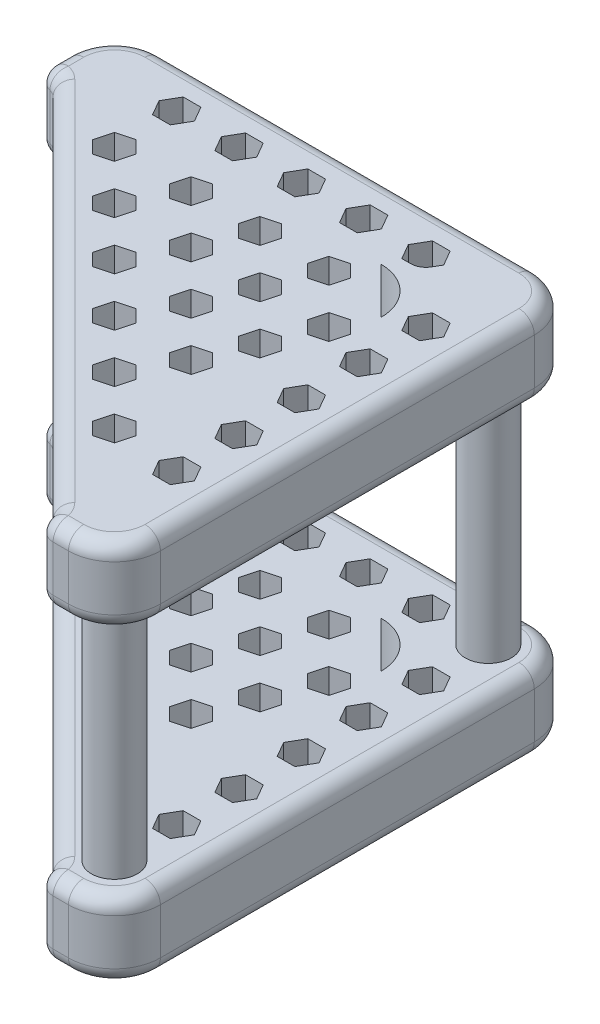
SolidWorks part; units mm, degrees
ref_plane "Front Plane" through (0, 0, 0) normal (0, 0, 1) x (1, 0, 0)
ref_plane "Top Plane" through (0, 0, 0) normal (0, 1, 0) x (1, 0, 0)
ref_plane "Right Plane" through (0, 0, 0) normal (1, 0, 0) x (0, 0, -1)
sketch "Sketch1" plane through (0, 0, 0) normal (0, 1, 0) x (1, 0, 0)
  line L0 (-9.7, 17.7) -> (14.7, 17.7)
  line L5 (17.7, -9.7) -> (17.7, 14.7)
  line L6 (-12.7, 14.7) -> (-12.7, 13.7)
  line L7 (13.7, -12.7) -> (14.7, -12.7)
  line L12 (-12.7, 14.7) -> (17.7, 14.7) construction
  line L13 (14.7, 17.7) -> (14.7, -12.7) construction
  line L14 (-4.4786, 14.7) -> (-5.056, 15.7)
  line L21 (-5.056, 15.7) -> (-6.2107, 15.7)
  line L22 (-6.2107, 15.7) -> (-6.788, 14.7)
  line L23 (-6.788, 14.7) -> (-6.2107, 13.7)
  line L24 (-6.2107, 13.7) -> (-5.056, 13.7)
  line L25 (-5.056, 13.7) -> (-4.4786, 14.7)
  line L26 (-0.412, 14.7) -> (-0.9893, 15.7)
  line L27 (-0.9893, 15.7) -> (-2.144, 15.7)
  line L28 (-2.144, 15.7) -> (-2.7214, 14.7)
  line L29 (-2.7214, 14.7) -> (-2.144, 13.7)
  line L30 (-2.144, 13.7) -> (-0.9893, 13.7)
  line L31 (-0.9893, 13.7) -> (-0.412, 14.7)
  line L32 (3.6547, 14.7) -> (3.0774, 15.7)
  line L33 (3.0774, 15.7) -> (1.9226, 15.7)
  line L34 (1.9226, 15.7) -> (1.3453, 14.7)
  line L35 (1.3453, 14.7) -> (1.9226, 13.7)
  line L36 (1.9226, 13.7) -> (3.0774, 13.7)
  line L37 (3.0774, 13.7) -> (3.6547, 14.7)
  line L38 (7.7214, 14.7) -> (7.144, 15.7)
  line L39 (7.144, 15.7) -> (5.9893, 15.7)
  line L40 (5.9893, 15.7) -> (5.412, 14.7)
  line L41 (5.412, 14.7) -> (5.9893, 13.7)
  line L42 (5.9893, 13.7) -> (7.144, 13.7)
  line L43 (7.144, 13.7) -> (7.7214, 14.7)
  line L44 (11.788, 14.7) -> (11.2107, 15.7)
  line L45 (11.2107, 15.7) -> (10.056, 15.7)
  line L46 (10.056, 15.7) -> (9.4786, 14.7)
  line L47 (9.4786, 14.7) -> (10.056, 13.7)
  line L48 (10.056, 13.7) -> (11.2107, 13.7)
  line L49 (11.2107, 13.7) -> (11.788, 14.7)
  line L56 (15.8547, 10.6333) -> (15.2774, 11.6333)
  line L57 (15.2774, 11.6333) -> (14.1226, 11.6333)
  line L58 (14.1226, 11.6333) -> (13.5453, 10.6333)
  line L59 (13.5453, 10.6333) -> (14.1226, 9.6333)
  line L60 (14.1226, 9.6333) -> (15.2774, 9.6333)
  line L61 (15.2774, 9.6333) -> (15.8547, 10.6333)
  line L62 (15.8547, 6.5667) -> (15.2774, 7.5667)
  line L63 (15.2774, 7.5667) -> (14.1226, 7.5667)
  line L64 (14.1226, 7.5667) -> (13.5453, 6.5667)
  line L65 (13.5453, 6.5667) -> (14.1226, 5.5667)
  line L66 (14.1226, 5.5667) -> (15.2774, 5.5667)
  line L67 (15.2774, 5.5667) -> (15.8547, 6.5667)
  line L68 (15.8547, 2.5) -> (15.2774, 3.5)
  line L69 (15.2774, 3.5) -> (14.1226, 3.5)
  line L70 (14.1226, 3.5) -> (13.5453, 2.5)
  line L71 (13.5453, 2.5) -> (14.1226, 1.5)
  line L72 (14.1226, 1.5) -> (15.2774, 1.5)
  line L73 (15.2774, 1.5) -> (15.8547, 2.5)
  line L74 (15.8547, -1.5667) -> (15.2774, -0.5667)
  line L75 (15.2774, -0.5667) -> (14.1226, -0.5667)
  line L76 (14.1226, -0.5667) -> (13.5453, -1.5667)
  line L77 (13.5453, -1.5667) -> (14.1226, -2.5667)
  line L78 (14.1226, -2.5667) -> (15.2774, -2.5667)
  line L79 (15.2774, -2.5667) -> (15.8547, -1.5667)
  line L80 (15.8547, -5.6333) -> (15.2774, -4.6333)
  line L81 (15.2774, -4.6333) -> (14.1226, -4.6333)
  line L82 (14.1226, -4.6333) -> (13.5453, -5.6333)
  line L83 (13.5453, -5.6333) -> (14.1226, -6.6333)
  line L84 (14.1226, -6.6333) -> (15.2774, -6.6333)
  line L85 (15.2774, -6.6333) -> (15.8547, -5.6333)
  line L92 (-11.4632, 12.4632) -> (12.4632, -11.4632)
  line L93 (9.7, 12.7) -> (12.7, 9.7)
  line L94 (-5.6333, 15.7) -> (-5.6333, 6.6333) construction
  line L95 (-5.6333, 6.6333) -> (15.8547, 10.6333) construction
  line L96 (-5.6333, 10.6333) -> (12.7, -7.7) construction
  line L97 (-1.6349, 6.6349) -> (-1.336, 7.7502)
  line L98 (-4.8168, 9.8168) -> (-4.518, 10.9322)
  line L99 (-4.518, 10.9322) -> (-5.3345, 11.7487)
  line L100 (-5.3345, 11.7487) -> (-6.4498, 11.4498)
  line L101 (-6.4498, 11.4498) -> (-6.7487, 10.3345)
  line L102 (-6.7487, 10.3345) -> (-5.9322, 9.518)
  line L103 (-5.9322, 9.518) -> (-4.8168, 9.8168)
  line L104 (-1.336, 7.7502) -> (-2.1525, 8.5667)
  line L105 (-2.1525, 8.5667) -> (-3.2678, 8.2678)
  line L106 (-3.2678, 8.2678) -> (-3.5667, 7.1525)
  line L107 (-3.5667, 7.1525) -> (-2.7502, 6.336)
  line L108 (-2.7502, 6.336) -> (-1.6349, 6.6349)
  line L109 (1.5471, 3.4529) -> (1.846, 4.5682)
  line L110 (1.846, 4.5682) -> (1.0295, 5.3847)
  line L111 (1.0295, 5.3847) -> (-0.0859, 5.0859)
  line L112 (-0.0859, 5.0859) -> (-0.3847, 3.9705)
  line L113 (-0.3847, 3.9705) -> (0.4318, 3.154)
  line L114 (0.4318, 3.154) -> (1.5471, 3.4529)
  line L115 (4.7291, 0.2709) -> (5.028, 1.3863)
  line L116 (5.028, 1.3863) -> (4.2115, 2.2027)
  line L117 (4.2115, 2.2027) -> (3.0961, 1.9039)
  line L118 (3.0961, 1.9039) -> (2.7973, 0.7885)
  line L119 (2.7973, 0.7885) -> (3.6137, -0.028)
  line L120 (3.6137, -0.028) -> (4.7291, 0.2709)
  line L121 (7.9111, -2.9111) -> (8.2099, -1.7957)
  line L122 (8.2099, -1.7957) -> (7.3934, -0.9792)
  line L123 (7.3934, -0.9792) -> (6.2781, -1.2781)
  line L124 (6.2781, -1.2781) -> (5.9792, -2.3934)
  line L125 (5.9792, -2.3934) -> (6.7957, -3.2099)
  line L126 (6.7957, -3.2099) -> (7.9111, -2.9111)
  line L127 (11.0931, -6.0931) -> (11.3919, -4.9777)
  line L128 (11.3919, -4.9777) -> (10.5754, -4.1612)
  line L129 (10.5754, -4.1612) -> (9.4601, -4.4601)
  line L130 (9.4601, -4.4601) -> (9.1612, -5.5754)
  line L131 (9.1612, -5.5754) -> (9.9777, -6.3919)
  line L132 (9.9777, -6.3919) -> (11.0931, -6.0931)
  line L133 (0.1832, 9.8168) -> (0.482, 10.9322)
  line L134 (0.482, 10.9322) -> (-0.3345, 11.7487)
  line L135 (-0.3345, 11.7487) -> (-1.4498, 11.4498)
  line L136 (-1.4498, 11.4498) -> (-1.7487, 10.3345)
  line L137 (-1.7487, 10.3345) -> (-0.9322, 9.518)
  line L138 (-0.9322, 9.518) -> (0.1832, 9.8168)
  line L139 (3.3651, 6.6349) -> (3.664, 7.7502)
  line L140 (3.664, 7.7502) -> (2.8475, 8.5667)
  line L141 (2.8475, 8.5667) -> (1.7322, 8.2678)
  line L142 (1.7322, 8.2678) -> (1.4333, 7.1525)
  line L143 (1.4333, 7.1525) -> (2.2498, 6.336)
  line L144 (2.2498, 6.336) -> (3.3651, 6.6349)
  line L145 (6.5471, 3.4529) -> (6.846, 4.5682)
  line L146 (6.846, 4.5682) -> (6.0295, 5.3847)
  line L147 (6.0295, 5.3847) -> (4.9141, 5.0859)
  line L148 (4.9141, 5.0859) -> (4.6153, 3.9705)
  line L149 (4.6153, 3.9705) -> (5.4318, 3.154)
  line L150 (5.4318, 3.154) -> (6.5471, 3.4529)
  line L151 (9.7291, 0.2709) -> (10.028, 1.3863)
  line L152 (10.028, 1.3863) -> (9.2115, 2.2027)
  line L153 (9.2115, 2.2027) -> (8.0961, 1.9039)
  line L154 (8.0961, 1.9039) -> (7.7973, 0.7885)
  line L155 (7.7973, 0.7885) -> (8.6137, -0.028)
  line L156 (8.6137, -0.028) -> (9.7291, 0.2709)
  line L157 (4.6832, 9.8168) -> (4.982, 10.9322)
  line L158 (4.982, 10.9322) -> (4.1655, 11.7487)
  line L159 (4.1655, 11.7487) -> (3.0502, 11.4498)
  line L160 (3.0502, 11.4498) -> (2.7513, 10.3345)
  line L161 (2.7513, 10.3345) -> (3.5678, 9.518)
  line L162 (3.5678, 9.518) -> (4.6832, 9.8168)
  line L163 (7.8651, 6.6349) -> (8.164, 7.7502)
  line L164 (8.164, 7.7502) -> (7.3475, 8.5667)
  line L165 (7.3475, 8.5667) -> (6.2322, 8.2678)
  line L166 (6.2322, 8.2678) -> (5.9333, 7.1525)
  line L167 (5.9333, 7.1525) -> (6.7498, 6.336)
  line L168 (6.7498, 6.336) -> (7.8651, 6.6349)
  line L169 (11.0471, 3.4529) -> (11.346, 4.5682)
  line L170 (11.346, 4.5682) -> (10.5295, 5.3847)
  line L171 (10.5295, 5.3847) -> (9.4141, 5.0859)
  line L172 (9.4141, 5.0859) -> (9.1153, 3.9705)
  line L173 (9.1153, 3.9705) -> (9.9318, 3.154)
  line L174 (9.9318, 3.154) -> (11.0471, 3.4529)
  line L175 (9.1832, 9.8168) -> (9.482, 10.9322)
  line L176 (9.482, 10.9322) -> (8.6655, 11.7487)
  line L177 (8.6655, 11.7487) -> (7.5502, 11.4498)
  line L178 (7.5502, 11.4498) -> (7.2513, 10.3345)
  line L179 (7.2513, 10.3345) -> (8.0678, 9.518)
  line L180 (8.0678, 9.518) -> (9.1832, 9.8168)
  line L181 (12.3651, 6.6349) -> (12.664, 7.7502)
  line L182 (12.664, 7.7502) -> (11.8475, 8.5667)
  line L183 (11.8475, 8.5667) -> (10.7322, 8.2678)
  line L184 (10.7322, 8.2678) -> (10.4333, 7.1525)
  line L185 (10.4333, 7.1525) -> (11.2498, 6.336)
  line L186 (11.2498, 6.336) -> (12.3651, 6.6349)
  arc A0 (9.7, 12.7) -> (12.7, 9.7) centre (9.7, 9.7) cw
  arc A1 (17.7, -9.7) -> (14.7, -12.7) centre (14.7, -9.7) cw
  arc A2 (14.7, 17.7) -> (17.7, 14.7) centre (14.7, 14.7) cw
  arc A3 (-9.7, 17.7) -> (-12.7, 14.7) centre (-9.7, 14.7) ccw
  arc A4 (13.7, -12.7) -> (12.728, -11.9351) centre (13.7, -11.7) cw
  arc A5 (-12.7, 13.7) -> (-11.9351, 12.728) centre (-11.7, 13.7) ccw
  circle A6 centre (-9.7, 14.7) radius 1.5
  circle A7 centre (14.7, -9.7) radius 1.5
  circle A8 centre (14.7, 14.7) radius 1.5
  circle A9 centre (-5.6333, 10.6333) radius 1 construction
  arc A10 (12.4632, -11.4632) -> (12.728, -11.9351) centre (11.7561, -12.1703) cw
  arc A11 (-11.4632, 12.4632) -> (-11.9351, 12.728) centre (-12.1703, 11.7561) ccw
  point P0 (0, 0)
  point P11 (12.7, 12.7)
  dimension "D4" = 3
  dimension "D5" = 3
  dimension "D6" = 3
  dimension "D7" = 3
  dimension "D2" = 1
  dimension "D1" = 1
  dimension "D8" = 2
  dimension "D3" = 1
  dimension "D13" = 1
  dimension "D9" = 6
  dimension "D10" = 2
  dimension "D11" = 2
  dimension "D12" = 2
extrude "Boss-Extrude1" add sketch "Sketch1" along normal blind 5
extrude "Boss-Extrude2" add sketch "Sketch1<2>" along normal blind 25 contours A8 | A6 | A7 region at (14.7, 0, -14.7)
sketch "Sketch1<2>" plane through (0, 0, 0) normal (0, 1, 0) x (1, 0, 0) same geometry as "Sketch1"
sketch "Sketch2" plane through (0, 25, 0) normal (0, 1, 0) x (1, 0, 0)
  line L0 (-9.7, 17.7) -> (14.7, 17.7)
  line L1 (17.7, -9.7) -> (17.7, 14.7)
  line L2 (-12.7, 14.7) -> (-12.7, 13.7)
  line L3 (13.7, -12.7) -> (14.7, -12.7)
  line L4 (-12.7, 14.7) -> (17.7, 14.7) construction
  line L5 (14.7, 17.7) -> (14.7, -12.7) construction
  line L6 (-4.4786, 14.7) -> (-5.056, 15.7)
  line L7 (-5.056, 15.7) -> (-6.2107, 15.7)
  line L8 (-6.2107, 15.7) -> (-6.788, 14.7)
  line L9 (-6.788, 14.7) -> (-6.2107, 13.7)
  line L10 (-6.2107, 13.7) -> (-5.056, 13.7)
  line L11 (-5.056, 13.7) -> (-4.4786, 14.7)
  line L12 (-0.412, 14.7) -> (-0.9893, 15.7)
  line L13 (-0.9893, 15.7) -> (-2.144, 15.7)
  line L14 (-2.144, 15.7) -> (-2.7214, 14.7)
  line L15 (-2.7214, 14.7) -> (-2.144, 13.7)
  line L16 (-2.144, 13.7) -> (-0.9893, 13.7)
  line L17 (-0.9893, 13.7) -> (-0.412, 14.7)
  line L18 (3.6547, 14.7) -> (3.0774, 15.7)
  line L19 (3.0774, 15.7) -> (1.9226, 15.7)
  line L20 (1.9226, 15.7) -> (1.3453, 14.7)
  line L21 (1.3453, 14.7) -> (1.9226, 13.7)
  line L22 (1.9226, 13.7) -> (3.0774, 13.7)
  line L23 (3.0774, 13.7) -> (3.6547, 14.7)
  line L24 (7.7214, 14.7) -> (7.144, 15.7)
  line L25 (7.144, 15.7) -> (5.9893, 15.7)
  line L26 (5.9893, 15.7) -> (5.412, 14.7)
  line L27 (5.412, 14.7) -> (5.9893, 13.7)
  line L28 (5.9893, 13.7) -> (7.144, 13.7)
  line L29 (7.144, 13.7) -> (7.7214, 14.7)
  line L30 (11.788, 14.7) -> (11.2107, 15.7)
  line L31 (11.2107, 15.7) -> (10.056, 15.7)
  line L32 (10.056, 15.7) -> (9.4786, 14.7)
  line L33 (9.4786, 14.7) -> (10.056, 13.7)
  line L34 (10.056, 13.7) -> (11.2107, 13.7)
  line L35 (11.2107, 13.7) -> (11.788, 14.7)
  line L36 (15.8547, 10.6333) -> (15.2774, 11.6333)
  line L37 (15.2774, 11.6333) -> (14.1226, 11.6333)
  line L38 (14.1226, 11.6333) -> (13.5453, 10.6333)
  line L39 (13.5453, 10.6333) -> (14.1226, 9.6333)
  line L40 (14.1226, 9.6333) -> (15.2774, 9.6333)
  line L41 (15.2774, 9.6333) -> (15.8547, 10.6333)
  line L42 (15.8547, 6.5667) -> (15.2774, 7.5667)
  line L43 (15.2774, 7.5667) -> (14.1226, 7.5667)
  line L44 (14.1226, 7.5667) -> (13.5453, 6.5667)
  line L45 (13.5453, 6.5667) -> (14.1226, 5.5667)
  line L46 (14.1226, 5.5667) -> (15.2774, 5.5667)
  line L47 (15.2774, 5.5667) -> (15.8547, 6.5667)
  line L48 (15.8547, 2.5) -> (15.2774, 3.5)
  line L49 (15.2774, 3.5) -> (14.1226, 3.5)
  line L50 (14.1226, 3.5) -> (13.5453, 2.5)
  line L51 (13.5453, 2.5) -> (14.1226, 1.5)
  line L52 (14.1226, 1.5) -> (15.2774, 1.5)
  line L53 (15.2774, 1.5) -> (15.8547, 2.5)
  line L54 (15.8547, -1.5667) -> (15.2774, -0.5667)
  line L55 (15.2774, -0.5667) -> (14.1226, -0.5667)
  line L56 (14.1226, -0.5667) -> (13.5453, -1.5667)
  line L57 (13.5453, -1.5667) -> (14.1226, -2.5667)
  line L58 (14.1226, -2.5667) -> (15.2774, -2.5667)
  line L59 (15.2774, -2.5667) -> (15.8547, -1.5667)
  line L60 (15.8547, -5.6333) -> (15.2774, -4.6333)
  line L61 (15.2774, -4.6333) -> (14.1226, -4.6333)
  line L62 (14.1226, -4.6333) -> (13.5453, -5.6333)
  line L63 (13.5453, -5.6333) -> (14.1226, -6.6333)
  line L64 (14.1226, -6.6333) -> (15.2774, -6.6333)
  line L65 (15.2774, -6.6333) -> (15.8547, -5.6333)
  line L66 (-11.4632, 12.4632) -> (12.4632, -11.4632)
  line L67 (9.7, 12.7) -> (12.7, 9.7)
  line L68 (-5.6333, 15.7) -> (-5.6333, 6.6333) construction
  line L69 (-5.6333, 6.6333) -> (15.8547, 10.6333) construction
  line L70 (-5.6333, 10.6333) -> (12.7, -7.7) construction
  line L71 (-1.6349, 6.6349) -> (-1.336, 7.7502)
  line L72 (-4.8168, 9.8168) -> (-4.518, 10.9322)
  line L73 (-4.518, 10.9322) -> (-5.3345, 11.7487)
  line L74 (-5.3345, 11.7487) -> (-6.4498, 11.4498)
  line L75 (-6.4498, 11.4498) -> (-6.7487, 10.3345)
  line L76 (-6.7487, 10.3345) -> (-5.9322, 9.518)
  line L77 (-5.9322, 9.518) -> (-4.8168, 9.8168)
  line L78 (-1.336, 7.7502) -> (-2.1525, 8.5667)
  line L79 (-2.1525, 8.5667) -> (-3.2678, 8.2678)
  line L80 (-3.2678, 8.2678) -> (-3.5667, 7.1525)
  line L81 (-3.5667, 7.1525) -> (-2.7502, 6.336)
  line L82 (-2.7502, 6.336) -> (-1.6349, 6.6349)
  line L83 (1.5471, 3.4529) -> (1.846, 4.5682)
  line L84 (1.846, 4.5682) -> (1.0295, 5.3847)
  line L85 (1.0295, 5.3847) -> (-0.0859, 5.0859)
  line L86 (-0.0859, 5.0859) -> (-0.3847, 3.9705)
  line L87 (-0.3847, 3.9705) -> (0.4318, 3.154)
  line L88 (0.4318, 3.154) -> (1.5471, 3.4529)
  line L89 (4.7291, 0.2709) -> (5.028, 1.3863)
  line L90 (5.028, 1.3863) -> (4.2115, 2.2027)
  line L91 (4.2115, 2.2027) -> (3.0961, 1.9039)
  line L92 (3.0961, 1.9039) -> (2.7973, 0.7885)
  line L93 (2.7973, 0.7885) -> (3.6137, -0.028)
  line L94 (3.6137, -0.028) -> (4.7291, 0.2709)
  line L95 (7.9111, -2.9111) -> (8.2099, -1.7957)
  line L96 (8.2099, -1.7957) -> (7.3934, -0.9792)
  line L97 (7.3934, -0.9792) -> (6.2781, -1.2781)
  line L98 (6.2781, -1.2781) -> (5.9792, -2.3934)
  line L99 (5.9792, -2.3934) -> (6.7957, -3.2099)
  line L100 (6.7957, -3.2099) -> (7.9111, -2.9111)
  line L101 (11.0931, -6.0931) -> (11.3919, -4.9777)
  line L102 (11.3919, -4.9777) -> (10.5754, -4.1612)
  line L103 (10.5754, -4.1612) -> (9.4601, -4.4601)
  line L104 (9.4601, -4.4601) -> (9.1612, -5.5754)
  line L105 (9.1612, -5.5754) -> (9.9777, -6.3919)
  line L106 (9.9777, -6.3919) -> (11.0931, -6.0931)
  line L107 (0.1832, 9.8168) -> (0.482, 10.9322)
  line L108 (0.482, 10.9322) -> (-0.3345, 11.7487)
  line L109 (-0.3345, 11.7487) -> (-1.4498, 11.4498)
  line L110 (-1.4498, 11.4498) -> (-1.7487, 10.3345)
  line L111 (-1.7487, 10.3345) -> (-0.9322, 9.518)
  line L112 (-0.9322, 9.518) -> (0.1832, 9.8168)
  line L113 (3.3651, 6.6349) -> (3.664, 7.7502)
  line L114 (3.664, 7.7502) -> (2.8475, 8.5667)
  line L115 (2.8475, 8.5667) -> (1.7322, 8.2678)
  line L116 (1.7322, 8.2678) -> (1.4333, 7.1525)
  line L117 (1.4333, 7.1525) -> (2.2498, 6.336)
  line L118 (2.2498, 6.336) -> (3.3651, 6.6349)
  line L119 (6.5471, 3.4529) -> (6.846, 4.5682)
  line L120 (6.846, 4.5682) -> (6.0295, 5.3847)
  line L121 (6.0295, 5.3847) -> (4.9141, 5.0859)
  line L122 (4.9141, 5.0859) -> (4.6153, 3.9705)
  line L123 (4.6153, 3.9705) -> (5.4318, 3.154)
  line L124 (5.4318, 3.154) -> (6.5471, 3.4529)
  line L125 (9.7291, 0.2709) -> (10.028, 1.3863)
  line L126 (10.028, 1.3863) -> (9.2115, 2.2027)
  line L127 (9.2115, 2.2027) -> (8.0961, 1.9039)
  line L128 (8.0961, 1.9039) -> (7.7973, 0.7885)
  line L129 (7.7973, 0.7885) -> (8.6137, -0.028)
  line L130 (8.6137, -0.028) -> (9.7291, 0.2709)
  line L131 (4.6832, 9.8168) -> (4.982, 10.9322)
  line L132 (4.982, 10.9322) -> (4.1655, 11.7487)
  line L133 (4.1655, 11.7487) -> (3.0502, 11.4498)
  line L134 (3.0502, 11.4498) -> (2.7513, 10.3345)
  line L135 (2.7513, 10.3345) -> (3.5678, 9.518)
  line L136 (3.5678, 9.518) -> (4.6832, 9.8168)
  line L137 (7.8651, 6.6349) -> (8.164, 7.7502)
  line L138 (8.164, 7.7502) -> (7.3475, 8.5667)
  line L139 (7.3475, 8.5667) -> (6.2322, 8.2678)
  line L140 (6.2322, 8.2678) -> (5.9333, 7.1525)
  line L141 (5.9333, 7.1525) -> (6.7498, 6.336)
  line L142 (6.7498, 6.336) -> (7.8651, 6.6349)
  line L143 (11.0471, 3.4529) -> (11.346, 4.5682)
  line L144 (11.346, 4.5682) -> (10.5295, 5.3847)
  line L145 (10.5295, 5.3847) -> (9.4141, 5.0859)
  line L146 (9.4141, 5.0859) -> (9.1153, 3.9705)
  line L147 (9.1153, 3.9705) -> (9.9318, 3.154)
  line L148 (9.9318, 3.154) -> (11.0471, 3.4529)
  line L149 (9.1832, 9.8168) -> (9.482, 10.9322)
  line L150 (9.482, 10.9322) -> (8.6655, 11.7487)
  line L151 (8.6655, 11.7487) -> (7.5502, 11.4498)
  line L152 (7.5502, 11.4498) -> (7.2513, 10.3345)
  line L153 (7.2513, 10.3345) -> (8.0678, 9.518)
  line L154 (8.0678, 9.518) -> (9.1832, 9.8168)
  line L155 (12.3651, 6.6349) -> (12.664, 7.7502)
  line L156 (12.664, 7.7502) -> (11.8475, 8.5667)
  line L157 (11.8475, 8.5667) -> (10.7322, 8.2678)
  line L158 (10.7322, 8.2678) -> (10.4333, 7.1525)
  line L159 (10.4333, 7.1525) -> (11.2498, 6.336)
  line L160 (11.2498, 6.336) -> (12.3651, 6.6349)
  arc A0 (9.7, 12.7) -> (12.7, 9.7) centre (9.7, 9.7) cw
  arc A1 (17.7, -9.7) -> (14.7, -12.7) centre (14.7, -9.7) cw
  arc A2 (14.7, 17.7) -> (17.7, 14.7) centre (14.7, 14.7) cw
  arc A3 (-9.7, 17.7) -> (-12.7, 14.7) centre (-9.7, 14.7) ccw
  arc A4 (13.7, -12.7) -> (12.728, -11.9351) centre (13.7, -11.7) cw
  arc A5 (-12.7, 13.7) -> (-11.9351, 12.728) centre (-11.7, 13.7) ccw
  circle A6 centre (-9.7, 14.7) radius 1.5
  circle A7 centre (14.7, -9.7) radius 1.5
  circle A8 centre (14.7, 14.7) radius 1.5
  circle A9 centre (-5.6333, 10.6333) radius 1 construction
  arc A10 (12.4632, -11.4632) -> (12.728, -11.9351) centre (11.7561, -12.1703) cw
  arc A11 (-11.4632, 12.4632) -> (-11.9351, 12.728) centre (-12.1703, 11.7561) ccw
  point P0 (0, 0)
  point P10 (12.7, 12.7)
  dimension "D1" = 3
  dimension "D2" = 3
  dimension "D3" = 3
  dimension "D4" = 3
  dimension "D5" = 1
  dimension "D6" = 1
  dimension "D8" = 1
  dimension "D9" = 1
  dimension "D7" = 2
extrude "Boss-Extrude3" add sketch "Sketch2" against normal blind 5
fillet "Fillet1" radius 1 49 edges at (-11.6809, 20, -12.6281) (-12.4859, 20, -13.0816) (-12.7, 20, -14.2) (-11.8213, 20, -16.8213) (2.5, 20, -17.7) (16.8213, 20, -16.8213) (17.7, 20, -2.5) (16.8213, 20, 11.8213) (14.2, 20, 12.7) (13.0816, 20, 12.4859) (12.6281, 20, 11.6809) (-11.6809, 5, -12.6281) (-12.4859, 5, -13.0816) (-12.7, 5, -14.2) (-11.8213, 5, -16.8213) (2.5, 5, -17.7) (16.8213, 5, -16.8213) (17.7, 5, -2.5) (16.8213, 5, 11.8213) (14.2, 5, 12.7) (13.0816, 5, 12.4859) (12.6281, 5, 11.6809) (-11.6809, 0, -12.6281) (-12.4859, 0, -13.0816) (-12.7, 0, -14.2) (-11.8213, 0, -16.8213) (2.5, 0, -17.7) (16.8213, 0, -16.8213) (17.7, 0, -2.5) (16.8213, 0, 11.8213) (14.2, 0, 12.7) (13.0816, 0, 12.4859) (12.6281, 0, 11.6809) (-11.6809, 25, -12.6281) (-12.4859, 25, -13.0816) (-12.7, 25, -14.2) (-11.8213, 25, -16.8213) (2.5, 25, -17.7) (16.8213, 25, -16.8213) (17.7, 25, -2.5) (16.8213, 25, 11.8213) (14.2, 25, 12.7) (13.0816, 25, 12.4859) (12.6281, 25, 11.6809) (0.5, 20, -0.5) (0.5, 5, -0.5) (0.5, 0, -0.5) (11.2107, 22.5, -13.7) (0.5, 25, -0.5)
